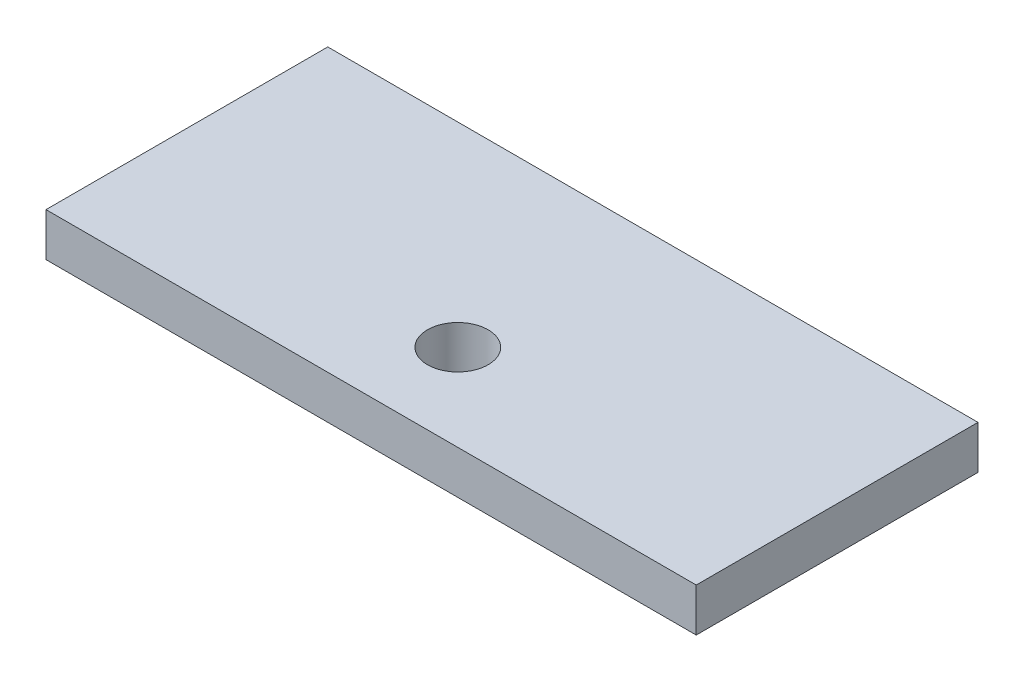
SolidWorks part; units mm, degrees
ref_plane "Front Plane" through (0, 0, 0) normal (0, 0, 1) x (1, 0, 0)
ref_plane "Top Plane" through (0, 0, 0) normal (0, 1, 0) x (1, 0, 0)
ref_plane "Right Plane" through (0, 0, 0) normal (1, 0, 0) x (0, 0, -1)
sketch "Sketch1" plane through (0, 0, 0) normal (0, 1, 0) x (1, 0, 0)
  line L1 (-75, -32.5) -> (75, -32.5)
  line L2 (-75, -32.5) -> (-75, 32.5)
  line L3 (-75, 32.5) -> (75, 32.5)
  line L4 (75, -32.5) -> (75, 32.5)
  line L5 (-75, -32.5) -> (75, 32.5) construction
  line L6 (-75, 32.5) -> (75, -32.5) construction
  point P0 (0, 0)
  dimension "D1" = 150
  dimension "D2" = 65
extrude "Boss-Extrude1" add sketch "Sketch1" along normal blind 10
sketch "Sketch2" plane through (0, 0, 0) normal (0, 1, 0) x (1, 0, 0)
  line L0 (0, -12.5) -> (0, 781.074) construction
  line L1 (-75, -32.5) -> (75, -32.5) construction
  line L2 (0, -12.5) -> (979.3965, -12.5) construction
  circle A0 centre (0, -12.5) radius 7
  dimension "D1" = 14
  dimension "D2" = 20
extrude "Cut-Extrude2" cut sketch "Sketch2" against normal through all and the other way through all
